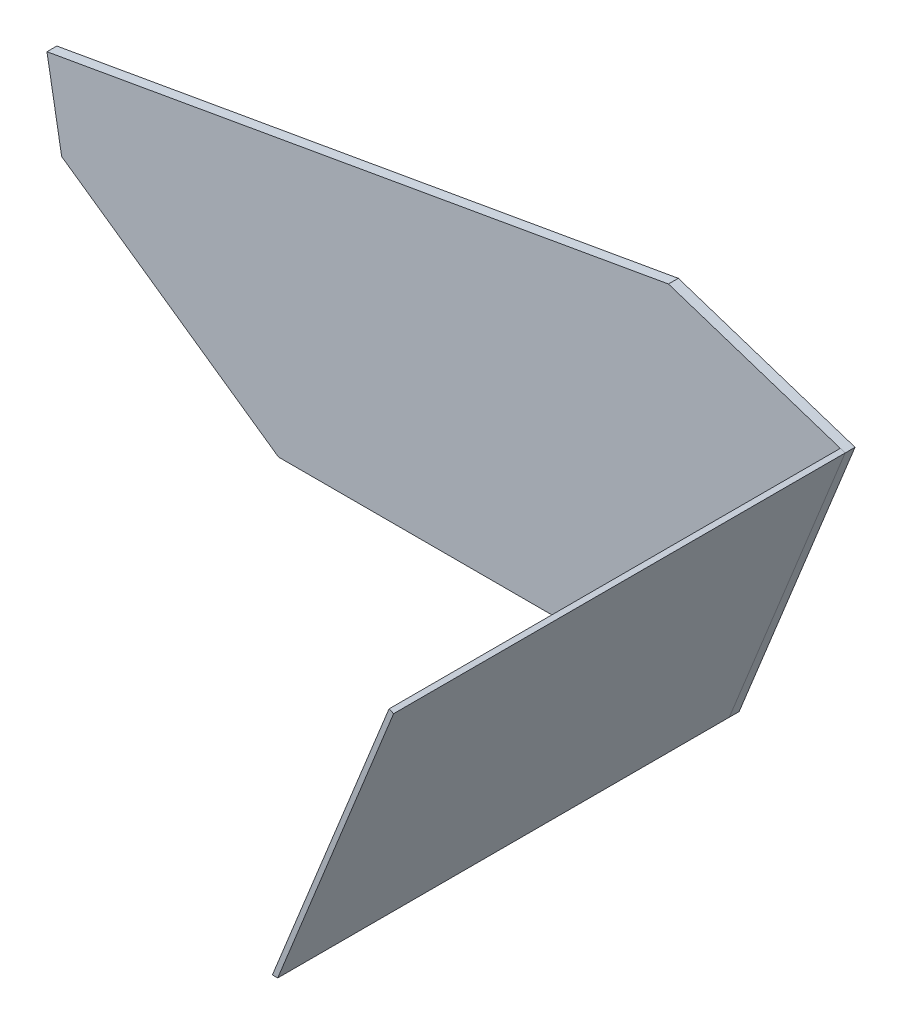
SolidWorks part; units mm, degrees
material "Melamine"
ref_plane "Front Plane" through (0, 0, 0) normal (0, 0, 1) x (1, 0, 0)
ref_plane "Top Plane" through (0, 0, 0) normal (0, 1, 0) x (1, 0, 0)
ref_plane "Right Plane" through (0, 0, 0) normal (1, 0, 0) x (0, 0, -1)
ref_axis "Axis1" through (0, 0, -14.8175) along (0, 0, 1)
sketch "Sketch1" plane through (0, 0, 0) normal (0, 0, 1) x (1, 0, 0)
  line L0 (-140, 0) -> (140, 0) construction
  line L1 (-140, 0) -> (-303.8304, 114.7153) construction
  line L4 (-151.0709, 0) -> (-307.4726, 109.5137) construction
  line L5 (-307.4726, 109.5137) -> (-303.8304, 114.7153) construction
  line L11 (140, 0) -> (143.4243, 0)
  line L12 (140, 0) -> (214.9213, 185.4368) construction
  line L14 (143.4243, 0) -> (217.8651, 184.2474)
  line L15 (217.8651, 184.2474) -> (214.9213, 185.4368)
  line L16 (214.9213, 185.4368) -> (140, 0)
  line L17 (-140, 0) -> (-151.0709, 0) construction
  point P3 (0, 0)
  point P4 (0, 0)
  point P8 (0, 0)
  dimension "D1" = 35
  dimension "D2" = 280
  dimension "D4" = 200
  dimension "D6" = 6.35
  dimension "D7" = 68
  dimension "D8" = 200
  dimension "D9" = 3.175
extrude "Boss-Extrude1" add sketch "Sketch1" along normal blind 290
sketch "Sketch2" plane through (0, 0, 0) normal (0, 0, 1) x (1, 0, 0)
  line L1 (-294.7779, 151.108) -> (104.3699, 221.4886)
  line L3 (143.4243, 0) -> (-146.0709, 0)
  line L4 (-146.0709, 0) -> (-285.3267, 97.508) construction
  line L5 (143.4243, 0) -> (217.8651, 184.2474)
  line L7 (-285.3267, 97.508) -> (-294.7779, 151.108)
  line L8 (-285.3267, 97.508) -> (-281.6845, 102.7096) construction
  line L9 (217.8651, 184.2474) -> (104.3699, 221.4886)
  line L10 (143.4243, 0) -> (104.3699, 221.4886) construction
  line L11 (-285.3267, 97.508) -> (-146.0709, 0)
  line L13 (-146.0709, 0) -> (-135, 0) construction
  line L14 (-285.3267, 97.508) -> (-146.0709, 0) construction
  line L15 (-281.6845, 102.7096) -> (-135, 0) construction
  dimension "D1" = 10
  dimension "D2" = 200
  dimension "D3" = 6.35
  dimension "D4" = 35
  dimension "D5" = 170
  dimension "D6" = 275
extrude "Boss-Extrude2" add sketch "Sketch2" against normal blind 6.35 separate body
ref_plane "Plane1" through (0, 0, 0) normal (0.9848, 0.1736, 0) x (0, 0, 1)
ref_point "Walls Center"
